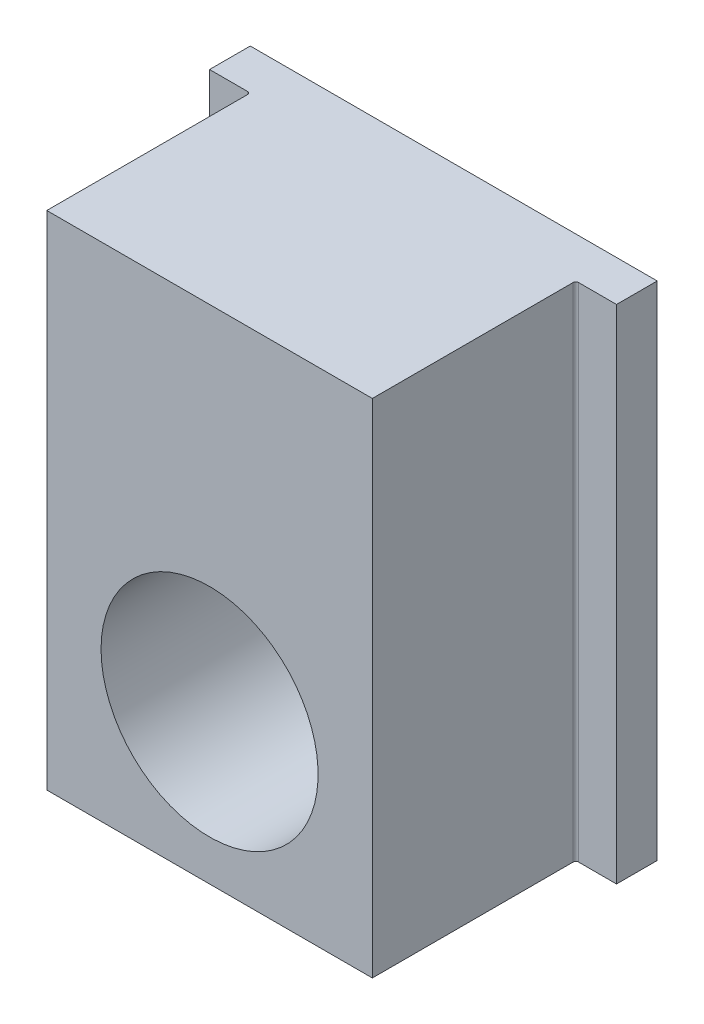
SolidWorks part; units mm, degrees
ref_plane "Piano frontale" through (0, 0, 0) normal (0, 0, 1) x (1, 0, 0)
ref_plane "Piano superiore" through (0, 0, 0) normal (0, 1, 0) x (1, 0, 0)
ref_plane "Piano destro" through (0, 0, 0) normal (1, 0, 0) x (0, 0, -1)
sketch "Schizzo1" plane through (0, 0, 0) normal (0, 1, 0) x (1, 0, 0)
  line L16 (0, 25.3009) -> (0, -18.5044) construction
  line L17 (-15, 13.5664) -> (15, 13.5664)
  line L18 (15, 13.5664) -> (15, 10.5664)
  line L19 (15, 10.5664) -> (12, 10.5664)
  line L20 (12, 10.5664) -> (12, -4.4336)
  line L21 (12, -4.4336) -> (-12, -4.4336)
  line L22 (-12, 10.5664) -> (-12, -4.4336)
  line L23 (-15, 10.5664) -> (-12, 10.5664)
  line L24 (-15, 13.5664) -> (-15, 10.5664)
  point P2 (0, -18.5044)
  point P10 (0, -4.4336)
  point P13 (0, 13.5664)
  dimension "D1" = 24
  dimension "D2" = 30
  dimension "D3" = 3
  dimension "D4" = 15
extrude "Estrusione-Estrusione1" add sketch "Schizzo1" along normal blind 37
sketch "Schizzo2" plane through (0, 0, -13.5664) normal (0, 0, -1) x (-1, 0, 0)
  line L0 (0, 0) -> (0, 41.8379) construction
  line L1 (-15, 0) -> (15, 0) construction
  circle A0 centre (0, 11) radius 8
  point P6 (-68.6102, 27.9369)
  dimension "D1" = 11
extrude "Taglio-Estrusione1" cut sketch "Schizzo2" against normal through all
fillet "Raccordo3" radius 0.2 1 edges at (-12, 18.5, -10.5664)
fillet "Raccordo4" radius 0.2 1 edges at (12, 18.5, -10.5664)
